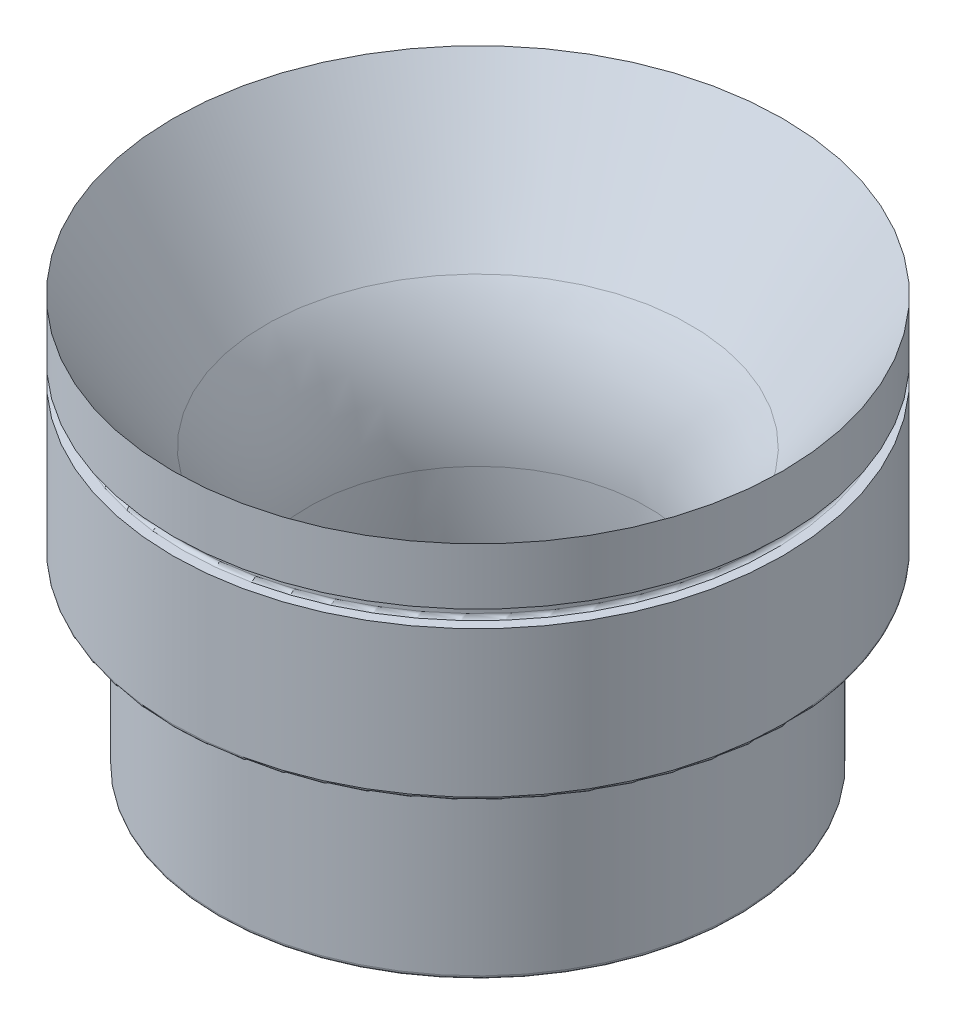
SolidWorks part; units mm, degrees
material "C (Graphite)"
ref_plane "Front Plane" through (0, 0, 0) normal (0, 0, 1) x (1, 0, 0)
ref_plane "Top Plane" through (0, 0, 0) normal (0, 1, 0) x (1, 0, 0)
ref_plane "Right Plane" through (0, 0, 0) normal (1, 0, 0) x (0, 0, -1)
sketch "Sketch4" plane through (0, 0, 0) normal (1, 0, 0) x (0, 0, -1)
  line L0 (0, 0) -> (0, -131.2074) construction
  line L1 (34.2773, 0) -> (23.8732, -14.8586)
  line L2 (19.05, -81.8573) -> (19.05, -89.5311) construction
  line L3 (22.2956, -54.8084) -> (51.1382, -162.4506) construction
  line L17 (34.2773, 0) -> (34.2773, -25.0505)
  line L18 (34.2773, -25.0505) -> (29.1846, -25.0505)
  line L19 (29.1846, -25.0505) -> (29.1846, -46.0309)
  line L20 (29.1846, -46.0309) -> (20.3822, -46.0309)
  arc A1 (23.8732, -14.8586) -> (19.05, -30.1559) centre (45.72, -30.1559) ccw construction
  arc A2 (19.05, -30.1559) -> (22.2956, -54.8084) centre (114.3, -30.1559) ccw construction
  arc A3 (19.05, -30.1559) -> (20.3822, -46.0309) centre (114.3, -30.1559) ccw
  arc A4 (19.05, -30.1559) -> (23.8732, -14.8586) centre (45.72, -30.1559) cw
  point P2 (23.8732, -15.2795)
  dimension "D4" = 26.67
  dimension "D6" = 95.25
  dimension "D3" = 35
  dimension "D5" = 38.1
  dimension "D7" = 15
  dimension "D15" = 3.2456
  dimension "D19" = 10.1346
  dimension "D20" = 5.1054
  dimension "D21" = 15.875
  dimension "D11" = 68.5546
  dimension "D24" = 58.3692
revolve "Revolve1" add sketch "Sketch4" angle 360 about L0
sketch "Sketch6" plane through (0, 0, 0) normal (1, 0, 0) x (0, 0, -1)
  line L0 (34.2773, -6.35) -> (32.766, -6.35)
  line L1 (32.766, -6.35) -> (32.766, -8.255)
  line L2 (32.766, -8.255) -> (34.2773, -8.255)
  line L3 (34.2773, -8.255) -> (34.2773, -6.35)
  line L5 (-34.2773, 0) -> (34.2773, 0) construction
  line L6 (0, 11.3644) -> (0, 4.9299) construction
  line L7 (-34.2773, 0) -> (34.2773, 0) construction
  dimension "D1" = 65.532
  dimension "D2" = 1.905
  dimension "D3" = 6.35
revolve "Spring Groove" cut sketch "Sketch6" angle 360 about L6
fillet "Tool Radius" radius 0.4064 5 edges at (0, -46.0309, 29.1846) (0, -25.0505, 34.2773) (0, -6.35, 32.766) (0, -8.255, 32.766) (0, -25.0505, 29.1846)
equation "\"Dc\"= 114.30mm"
equation "\"Dt\"= 38.1mm"
equation "\"R1\"= 26.67mm"
equation "\"R2\"= 92mm"
equation "\"b\"= 35deg"
equation "\"Rn\"= 95.25mm"
equation "\"Tn\"= 15deg"
equation "\"Te\"= 3deg"
equation "\"De\"= 87.31mm"
equation "\"Le\"= 146.71mm"
equation "\"D5@Sketch4\"=\"Dt\""
equation "\"WallThickness\"=0.5"
equation "\"D20@Sketch4\"=0.200in+.001in"
equation "\"Rt\"=1.5"
